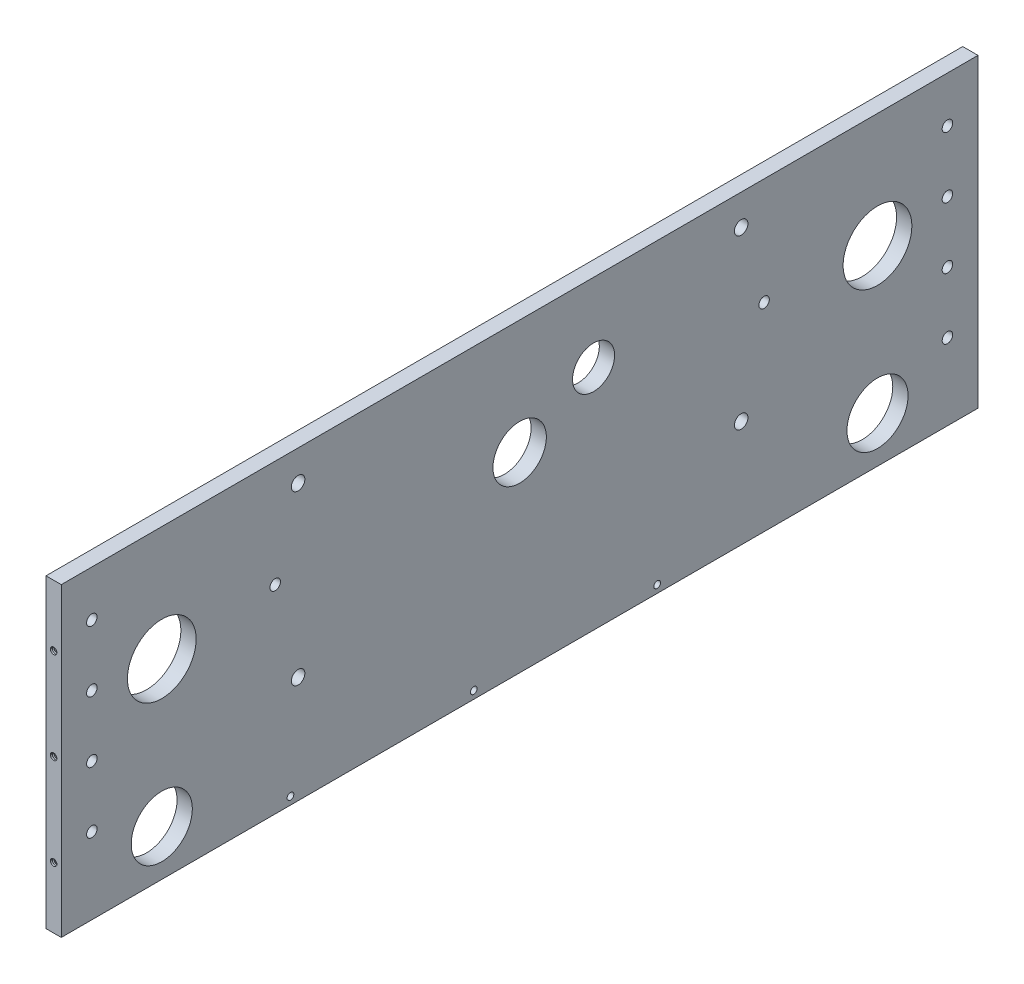
SolidWorks part; units mm, degrees
material "6061-T6 (SS)"
ref_plane "Front Plane" through (0, 0, 0) normal (0, 0, 1) x (1, 0, 0)
ref_plane "Top Plane" through (0, 0, 0) normal (0, 1, 0) x (1, 0, 0)
ref_plane "Right Plane" through (0, 0, 0) normal (1, 0, 0) x (0, 0, -1)
sketch "Sketch1" plane through (0, 0, 0) normal (1, 0, 0) x (0, 0, -1)
  line L1 (-190.5, 63.5) -> (190.5, 63.5)
  line L2 (-190.5, 63.5) -> (-190.5, -63.5)
  line L3 (-190.5, -63.5) -> (190.5, -63.5)
  line L4 (190.5, 63.5) -> (190.5, -63.5)
  line L5 (-190.5, 63.5) -> (190.5, -63.5) construction
  line L6 (-190.5, -63.5) -> (190.5, 63.5) construction
  point P0 (0, 0)
  dimension "D1" = 127
  dimension "D2" = 381
extrude "Boss-Extrude1" add sketch "Sketch1" along normal blind 6.35
sketch "Sketch2" plane through (6.35, 0, 0) normal (1, 0, 0) x (0, 0, -1)
  line L0 (-190.5, -63.5) -> (190.5, -63.5) construction
  line L1 (-148.7297, 15.875) -> (0, 15.875) construction
  line L2 (-74.3648, -34.925) -> (-74.3648, 15.875) construction
  line L3 (0, 15.875) -> (148.7297, 15.875) construction
  line L4 (74.3648, -34.925) -> (74.3648, 15.875) construction
  line L5 (190.5, 63.5) -> (-190.5, 63.5) construction
  line L6 (65.278, 53.34) -> (-56.642, 53.34) construction
  line L7 (65.278, 53.34) -> (65.278, -13.97) construction
  line L8 (65.278, -13.97) -> (-56.642, -13.97) construction
  line L9 (-56.642, 53.34) -> (-56.642, -13.97) construction
  line L10 (-190.5, -63.5) -> (190.5, -63.5) construction
  circle A1 centre (-148.7297, 15.875) radius 14.2875
  circle A2 centre (148.7297, 15.875) radius 14.2875
  circle A3 centre (-148.7297, 15.875) radius 38.1 construction
  circle A4 centre (0, 15.875) radius 38.1 construction
  circle A5 centre (148.7297, 15.875) radius 38.1 construction
  circle A6 centre (-74.3648, -34.925) radius 6.35 construction
  circle A7 centre (74.3648, -34.925) radius 6.35 construction
  circle A8 centre (-74.3648, 9.525) radius 6.35 construction
  circle A9 centre (74.3648, 9.525) radius 6.35 construction
  circle A11 centre (-148.7297, -44.4161) radius 12.7
  circle A12 centre (148.7297, -44.4161) radius 12.7
  circle A13 centre (0, 15.875) radius 29.2138 construction
  circle A14 centre (30.7215, 31.115) radius 5.08 construction
  circle A15 centre (30.7215, 31.115) radius 8.75
  circle A16 centre (0, 15.875) radius 11.1125
  point P11 (0, 0)
  dimension "D1" = 28.575
  dimension "D5" = 76.2
  dimension "D7" = 12.7
  dimension "D14" = 25.4
  dimension "D15" = 19.0839
  dimension "D17" = 25.4
  dimension "D20" = 58.4276
  dimension "D21" = 10.16
  dimension "D22" = 17.5001
  dimension "D24" = 22.225
  dimension "D25" = 28.575
  dimension "D2" = 79.375
  dimension "D3" = 148.7297
  dimension "D4" = 148.7297
  dimension "D6" = 0
  dimension "D8" = 28.575
  dimension "D9" = 44.45
  dimension "D10" = 56.642
  dimension "D11" = 121.92
  dimension "D12" = 10.16
  dimension "D13" = 49.53
  dimension "D16" = 148.7297
  dimension "D18" = 19.0839
  dimension "D19" = 148.7297
  dimension "D23" = 15.24
extrude "Cut-Extrude1" cut sketch "Sketch2" against normal through all
sketch "Sketch3" plane through (6.35, 0, 0) normal (1, 0, 0) x (0, 0, -1)
  line L0 (-184.404, 19.05) -> (-184.404, -19.05) construction
  line L1 (-190.5, 63.5) -> (-190.5, -63.5) construction
  point P2 (-184.404, 0)
  point P3 (-190.5, 0)
  dimension "D1" = 38.1
  dimension "D2" = 6.096
sketch "Sketch24" plane through (0, 0, 0) normal (-1, 0, 0) x (0, 0, 1)
  line L0 (-190.5, -63.5) -> (-190.5, 63.5) construction
  line L1 (-190.5, 63.5) -> (190.5, 63.5) construction
  point P0 (-92.075, -19.05)
  point P1 (-92.075, 50.8)
  point P2 (92.075, -19.05)
  point P4 (92.075, 50.8)
  dimension "D1" = 12.7
  dimension "D2" = 98.425
  dimension "D3" = 184.15
  dimension "D4" = 12.7
  dimension "D5" = 69.85
  dimension "D6" = 69.85
hole_wizard "CSK for #10 Flat Head Machine Screw2" positions "Sketch25" profile "Sketch26" countersink size "#10" standard "ANSI Inch" end condition through all
sketch "Sketch25" plane through (0, 0, 0) normal (-1, 0, 0) x (0, 0, 1)
  point P0 (-92.075, 50.8)
  point P3 (-92.075, -19.05)
  point P6 (92.075, -19.05)
  point P9 (92.075, 50.8)
sketch "Sketch26" plane through (0, 50.8, -92.075) normal (0, 1, 0) x (0, 0, 1)
  line L0 (0, 0) -> (0, 6.35)
  line L1 (0, 6.35) -> (2.8067, 6.35)
  line L2 (2.8067, 6.35) -> (2.8067, 2.396)
  line L3 (2.8067, 2.396) -> (4.8895, 0)
  line L5 (4.8895, 0) -> (0, 0)
  line L6 (-2.8067, 2.396) -> (-4.8895, 0) construction
  line L11 (0, -6.35) -> (0, 107.95) construction
  dimension "Thru Hole Dia." = 5.6134
  dimension "Thru Hole Depth" = 6.35
  dimension "Near C'Sink Dia." = 9.779
  dimension "Near C'Sink Angle" = 82
sketch "Sketch30" plane through (6.35, 0, 0) normal (1, 0, 0) x (0, 0, -1)
  line L0 (-190.5, -63.5) -> (190.5, -63.5) construction
  line L1 (-190.5, 63.5) -> (-190.5, -63.5) construction
  line L2 (190.5, -63.5) -> (190.5, 63.5) construction
  point P0 (-177.8, -57.15)
  point P1 (-177.8, -31.75)
  point P2 (-177.8, -6.35)
  point P3 (-177.8, 19.05)
  point P4 (-177.8, 44.45)
  point P5 (177.8, -57.15)
  point P6 (177.8, -31.75)
  point P7 (177.8, -6.35)
  point P8 (177.8, 19.05)
  point P9 (177.8, 44.45)
  dimension "D1" = 25.4
  dimension "D2" = 25.4
  dimension "D3" = 25.4
  dimension "D4" = 25.4
  dimension "D5" = 25.4
  dimension "D6" = 25.4
  dimension "D7" = 25.4
  dimension "D8" = 25.4
  dimension "D9" = 6.35
  dimension "D10" = 12.7
  dimension "D11" = 6.35
  dimension "D12" = 12.7
hole_wizard "11/64 (0.17188) Diameter Hole1" positions "Sketch31" profile "Sketch32" hole size "11/64" standard "ANSI Inch" end condition through all
sketch "Sketch31" plane through (6.35, 0, 0) normal (1, 0, 0) x (0, 0, -1)
  point P3 (-177.8, -31.75)
  point P6 (-177.8, -6.35)
  point P9 (-177.8, 19.05)
  point P12 (177.8, 19.05)
  point P15 (177.8, -6.35)
  point P18 (177.8, -31.75)
  point P25 (-177.8, 44.45)
  point P28 (177.8, 44.45)
sketch "Sketch32" plane through (6.35, -31.75, 177.8) normal (0, 1, 0) x (0, 0, -1)
  line L0 (0, 0) -> (0, 6.35)
  line L1 (0, 6.35) -> (2.1829, 6.35)
  line L2 (2.1829, 6.35) -> (2.1829, 0)
  line L5 (2.1829, 0) -> (0, 0)
  line L11 (0, -6.35) -> (0, 107.95) construction
  dimension "Thru Hole Dia." = 4.3658
  dimension "Thru Hole Depth" = 6.35
sketch "Sketch33" plane through (6.35, 0, 0) normal (1, 0, 0) x (0, 0, -1)
  line L1 (-190.5, 63.5) -> (-190.5, -63.5) construction
  line L2 (190.5, 63.5) -> (-190.5, 63.5) construction
  line L3 (190.5, -63.5) -> (190.5, 63.5) construction
  point P0 (-101.6, 19.05)
  point P1 (101.6, 19.05)
  dimension "D1" = 88.9
  dimension "D2" = 88.9
  dimension "D3" = 44.45
hole_wizard "11/64 (0.17188) Diameter Hole2" positions "Sketch34" profile "Sketch35" hole size "11/64" standard "ANSI Inch"
sketch "Sketch34" plane through (6.35, 0, 0) normal (1, 0, 0) x (0, 0, -1)
  point P0 (-101.6, 19.05)
  point P3 (101.6, 19.05)
sketch "Sketch35" plane through (6.35, 19.05, 101.6) normal (0, 1, 0) x (0, 0, -1)
  line L0 (0, 0) -> (0, 10.2016)
  line L1 (0, 10.2016) -> (2.1829, 8.89)
  line L2 (2.1829, 8.89) -> (2.1829, 0)
  line L5 (2.1829, 0) -> (0, 0)
  line L10 (0, 10.2016) -> (-2.1829, 8.89) construction
  line L11 (0, -6.35) -> (0, 107.95) construction
  dimension "Hole Dia." = 4.3658
  dimension "Hole Depth" = 8.89
  dimension "Drill Angle" = 118
sketch "Sketch36" plane through (6.35, 0, 0) normal (1, 0, 0) x (0, 0, -1)
  line L1 (-190.5, -63.5) -> (190.5, -63.5) construction
  line L2 (190.5, -63.5) -> (190.5, 63.5) construction
  point P0 (-95.25, -60.325)
  point P1 (-19.05, -60.325)
  point P2 (57.15, -60.325)
  dimension "D1" = 133.35
  dimension "D2" = 76.2
  dimension "D3" = 76.2
  dimension "D4" = 3.175
hole_wizard "#35 (0.11) Diameter Hole1" positions "Sketch37" profile "Sketch38" hole size "#35" standard "ANSI Inch"
sketch "Sketch37" plane through (6.35, 0, 0) normal (1, 0, 0) x (0, 0, -1)
  point P0 (-95.25, -60.325)
  point P3 (-19.05, -60.325)
  point P6 (57.15, -60.325)
sketch "Sketch38" plane through (6.35, -60.325, 95.25) normal (0, 1, 0) x (0, 0, -1)
  line L0 (0, 0) -> (0, 9.7294)
  line L1 (0, 9.7294) -> (1.397, 8.89)
  line L2 (1.397, 8.89) -> (1.397, 0)
  line L5 (1.397, 0) -> (0, 0)
  line L10 (0, 9.7294) -> (-1.397, 8.89) construction
  line L11 (0, -6.35) -> (0, 107.95) construction
  dimension "Hole Dia." = 2.794
  dimension "Hole Depth" = 8.89
  dimension "Drill Angle" = 118
sketch "Sketch39" plane through (0, 0, 190.5) normal (0, 0, 1) x (1, 0, 0)
  line L0 (6.35, 63.5) -> (0, 63.5) construction
  line L1 (6.35, 63.5) -> (6.35, -63.5) construction
  point P0 (3.175, 38.1)
  point P1 (3.175, 0)
  point P2 (3.175, -38.1)
  dimension "D1" = 25.4
  dimension "D2" = 3.175
hole_wizard "#36 (0.1065) Diameter Hole2" positions "Sketch40" profile "Sketch41" hole size "#36" standard "ANSI Inch"
sketch "Sketch40" plane through (0, 0, 190.5) normal (0, 0, 1) x (1, 0, 0)
  point P0 (3.175, 38.1)
  point P3 (3.175, 0)
  point P6 (3.175, -38.1)
sketch "Sketch41" plane through (3.175, 38.1, 190.5) normal (1, 0, 0) x (0, -1, 0)
  line L0 (0, 0) -> (0, 9.7027)
  line L1 (0, 9.7027) -> (1.3525, 8.89)
  line L2 (1.3525, 8.89) -> (1.3525, 0)
  line L5 (1.3525, 0) -> (0, 0)
  line L10 (0, 9.7027) -> (-1.3525, 8.89) construction
  line L11 (0, -6.35) -> (0, 107.95) construction
  dimension "Hole Dia." = 2.7051
  dimension "Hole Depth" = 8.89
  dimension "Drill Angle" = 118
thread "Thread1" pitch 0.7937 method cut profile "Thread Profile1" start angle 0, offset 0, length 6.35, pitch 0.7937, diameter 2.7051
ref_plane "Plane1" through (1.8225, 38.1, 190.5) normal (0, -1, 0) x (-1, 0, 0)
sketch "Thread Profile1" plane through (1.8225, 38.1, 190.5) normal (0, -1, 0) x (-1, 0, 0)
  line L0 (0, 0) -> (0, 0.7937) construction
  line L1 (0, 0) -> (0.4296, 0.248)
  line L2 (0.4296, 0.248) -> (0.4296, 0.3473)
  line L3 (0.4296, 0.3473) -> (0, 0.5953)
  line L4 (0.4296, 0.2977) -> (0, 0.2977) construction
  line L11 (0, 0) -> (0, 0.5953)
  point P2 (0, 0)
  dimension "Pitch" = 0.7937
  dimension "Profile_Angle" = 60
  dimension "Profile_Land" = 0.0992
  dimension "Profile_Height" = 0.4296
thread "Thread2" pitch 0.7937 method cut profile "Thread Profile2" start angle 0, offset 0, length 6.35, pitch 0.7937, diameter 2.7051
ref_plane "Plane2" through (1.8225, 0, 190.5) normal (0, -1, 0) x (-1, 0, 0)
sketch "Thread Profile2" plane through (1.8225, 0, 190.5) normal (0, -1, 0) x (-1, 0, 0)
  line L0 (0, 0) -> (0, 0.7937) construction
  line L1 (0, 0) -> (0.4296, 0.248)
  line L2 (0.4296, 0.248) -> (0.4296, 0.3473)
  line L3 (0.4296, 0.3473) -> (0, 0.5953)
  line L4 (0.4296, 0.2977) -> (0, 0.2977) construction
  line L11 (0, 0) -> (0, 0.5953)
  point P2 (0, 0)
  dimension "Pitch" = 0.7937
  dimension "Profile_Angle" = 60
  dimension "Profile_Land" = 0.0992
  dimension "Profile_Height" = 0.4296
thread "Thread3" pitch 0.7937 method cut profile "Thread Profile3" start angle 0, offset 0, length 6.35, pitch 0.7937, diameter 2.7051
ref_plane "Plane3" through (1.8225, -38.1, 190.5) normal (0, -1, 0) x (-1, 0, 0)
sketch "Thread Profile3" plane through (1.8225, -38.1, 190.5) normal (0, -1, 0) x (-1, 0, 0)
  line L0 (0, 0) -> (0, 0.7937) construction
  line L1 (0, 0) -> (0.4296, 0.248)
  line L2 (0.4296, 0.248) -> (0.4296, 0.3473)
  line L3 (0.4296, 0.3473) -> (0, 0.5953)
  line L4 (0.4296, 0.2977) -> (0, 0.2977) construction
  line L11 (0, 0) -> (0, 0.5953)
  point P2 (0, 0)
  dimension "Pitch" = 0.7937
  dimension "Profile_Angle" = 60
  dimension "Profile_Land" = 0.0992
  dimension "Profile_Height" = 0.4296
sketch "Sketch48" plane through (0, 0, -190.5) normal (0, 0, -1) x (-1, 0, 0)
  line L0 (-6.35, 63.5) -> (0, 63.5) construction
  line L1 (-6.35, -63.5) -> (-6.35, 63.5) construction
  point P0 (-3.175, 38.1)
  point P1 (-3.175, 0)
  point P2 (-3.175, -38.1)
  dimension "D1" = 25.4
  dimension "D2" = 3.175
  dimension "D3" = 38.1
  dimension "D4" = 38.1
hole_wizard "#36 (0.1065) Diameter Hole3" positions "Sketch49" profile "Sketch50" hole size "#36" standard "ANSI Inch"
sketch "Sketch49" plane through (0, 0, -190.5) normal (0, 0, -1) x (-1, 0, 0)
  point P0 (-3.175, 38.1)
  point P3 (-3.175, 0)
  point P6 (-3.175, -38.1)
sketch "Sketch50" plane through (3.175, 38.1, -190.5) normal (1, 0, 0) x (0, 1, 0)
  line L0 (0, 0) -> (0, 9.7027)
  line L1 (0, 9.7027) -> (1.3525, 8.89)
  line L2 (1.3525, 8.89) -> (1.3525, 0)
  line L5 (1.3525, 0) -> (0, 0)
  line L10 (0, 9.7027) -> (-1.3525, 8.89) construction
  line L11 (0, -6.35) -> (0, 107.95) construction
  dimension "Hole Dia." = 2.7051
  dimension "Hole Depth" = 8.89
  dimension "Drill Angle" = 118
thread "Thread4" pitch 0.7937 method cut profile "Thread Profile4" start angle 0, offset 0, length 6.35, pitch 0.7937, diameter 2.7051
ref_plane "Plane4" through (4.5275, 38.1, -190.5) normal (0, -1, 0) x (1, 0, 0)
sketch "Thread Profile4" plane through (4.5275, 38.1, -190.5) normal (0, -1, 0) x (1, 0, 0)
  line L0 (0, 0) -> (0, 0.7937) construction
  line L1 (0, 0) -> (0.4296, 0.248)
  line L2 (0.4296, 0.248) -> (0.4296, 0.3473)
  line L3 (0.4296, 0.3473) -> (0, 0.5953)
  line L4 (0.4296, 0.2977) -> (0, 0.2977) construction
  line L11 (0, 0) -> (0, 0.5953)
  point P2 (0, 0)
  dimension "Pitch" = 0.7937
  dimension "Profile_Angle" = 60
  dimension "Profile_Land" = 0.0992
  dimension "Profile_Height" = 0.4296
thread "Thread5" pitch 0.7937 method cut profile "Thread Profile5" start angle 0, offset 0, length 6.35, pitch 0.7937, diameter 2.7051
ref_plane "Plane5" through (4.5275, 0, -190.5) normal (0, -1, 0) x (1, 0, 0)
sketch "Thread Profile5" plane through (4.5275, 0, -190.5) normal (0, -1, 0) x (1, 0, 0)
  line L0 (0, 0) -> (0, 0.7937) construction
  line L1 (0, 0) -> (0.4296, 0.248)
  line L2 (0.4296, 0.248) -> (0.4296, 0.3473)
  line L3 (0.4296, 0.3473) -> (0, 0.5953)
  line L4 (0.4296, 0.2977) -> (0, 0.2977) construction
  line L11 (0, 0) -> (0, 0.5953)
  point P2 (0, 0)
  dimension "Pitch" = 0.7937
  dimension "Profile_Angle" = 60
  dimension "Profile_Land" = 0.0992
  dimension "Profile_Height" = 0.4296
thread "Thread6" pitch 0.7937 method cut profile "Thread Profile6" start angle 0, offset 0, length 6.35, pitch 0.7937, diameter 2.7051
ref_plane "Plane6" through (4.5275, -38.1, -190.5) normal (0, -1, 0) x (1, 0, 0)
sketch "Thread Profile6" plane through (4.5275, -38.1, -190.5) normal (0, -1, 0) x (1, 0, 0)
  line L0 (0, 0) -> (0, 0.7937) construction
  line L1 (0, 0) -> (0.4296, 0.248)
  line L2 (0.4296, 0.248) -> (0.4296, 0.3473)
  line L3 (0.4296, 0.3473) -> (0, 0.5953)
  line L4 (0.4296, 0.2977) -> (0, 0.2977) construction
  line L11 (0, 0) -> (0, 0.5953)
  point P2 (0, 0)
  dimension "Pitch" = 0.7937
  dimension "Profile_Angle" = 60
  dimension "Profile_Land" = 0.0992
  dimension "Profile_Height" = 0.4296
